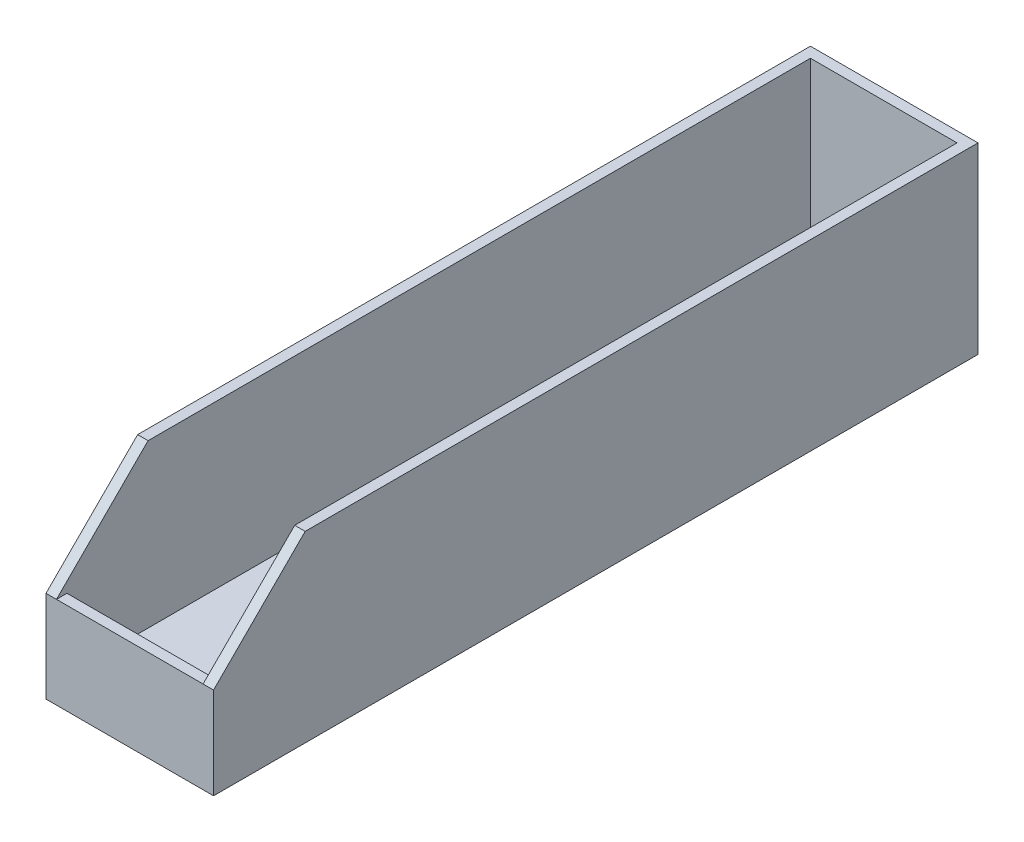
SolidWorks part; units mm, degrees
ref_plane "Front Plane" through (0, 0, 0) normal (0, 0, 1) x (1, 0, 0)
ref_plane "Top Plane" through (0, 0, 0) normal (0, 1, 0) x (1, 0, 0)
ref_plane "Right Plane" through (0, 0, 0) normal (1, 0, 0) x (0, 0, -1)
sketch "Sketch1" plane through (0, 0, 0) normal (0, 1, 0) x (1, 0, 0)
  line L0 (-14, -71) -> (-14, -73)
  line L1 (-16, 73) -> (16, 73)
  line L2 (-16, 73) -> (-16, -73)
  line L3 (-16, -73) -> (16, -73)
  line L4 (16, 73) -> (16, -73)
  line L5 (-16, 73) -> (16, -73) construction
  line L6 (-16, -73) -> (16, 73) construction
  line L7 (-14, 71) -> (14, 71)
  line L8 (-14, 71) -> (-14, -71)
  line L9 (-14, -71) -> (14, -71)
  line L10 (14, 71) -> (14, -71)
  line L11 (-14, 71) -> (14, -71) construction
  line L12 (-14, -71) -> (14, 71) construction
  line L13 (14, -71) -> (14, -73)
  point P0 (0, 0)
  point P6 (0, 0)
  dimension "D1" = 146
  dimension "D2" = 28
  dimension "D3" = 32
  dimension "D4" = 142
extrude "Boss-Extrude1" add sketch "Sketch1" along normal blind 4 contours L10 L7 L8 L9 region at (0, 0, 0)
extrude "Boss-Extrude2" add sketch "Sketch1<4>" along normal blind 35 contours L10 L13 L3 L4 L1 L2 L0 L8 L7 region at (-15.4947, 0, 72)
sketch "Sketch1<4>" plane through (0, 0, 0) normal (0, 1, 0) x (1, 0, 0) same geometry as "Sketch1"
extrude "Boss-Extrude3" add sketch "Sketch1<5>" along normal blind 17.5 contours L13 L9 L0 L3 region at (0, 0, 72)
sketch "Sketch1<5>" plane through (0, 0, 0) normal (0, 1, 0) x (1, 0, 0) same geometry as "Sketch1"
sketch "Sketch2" plane through (0, 4, 0) normal (0, 1, 0) x (1, 0, 0)
  line L0 (0, 30) -> (0, -30) construction
  circle A0 centre (0, 30) radius 2.5
  circle A1 centre (0, 30) radius 1.7
  circle A2 centre (0, -30) radius 2.5
  circle A3 centre (0, -30) radius 1.7
  point P6 (0, 0)
  dimension "D1" = 3.4
  dimension "D2" = 5
  dimension "D3" = 30
extrude "Cut-Extrude1" cut sketch "Sketch2" against normal up to next contours A1 | A3 region at (0, 4, -30) region at (0, 4, 30)
extrude "Cut-Extrude2" cut sketch "Sketch2<3>" against normal blind 2 contours A2 A3 | A1 A0 region at (-2.4293, 4, -30) region at (-2.4293, 4, 30)
sketch "Sketch2<3>" plane through (0, 4, 0) normal (0, 1, 0) x (1, 0, 0) same geometry as "Sketch2"
sketch "Sketch3" plane through (16, 0, 0) normal (1, 0, 0) x (0, 0, -1)
  line L0 (-73, 17.5) -> (-55.5, 35)
  line L1 (-73, 35) -> (-73, 0) construction
  line L2 (73, 35) -> (-73, 35) construction
  line L3 (-55.5, 35) -> (-73, 35)
  line L4 (-73, 35) -> (-73, 17.5)
extrude "Cut-Extrude3" cut sketch "Sketch3" against normal through all
